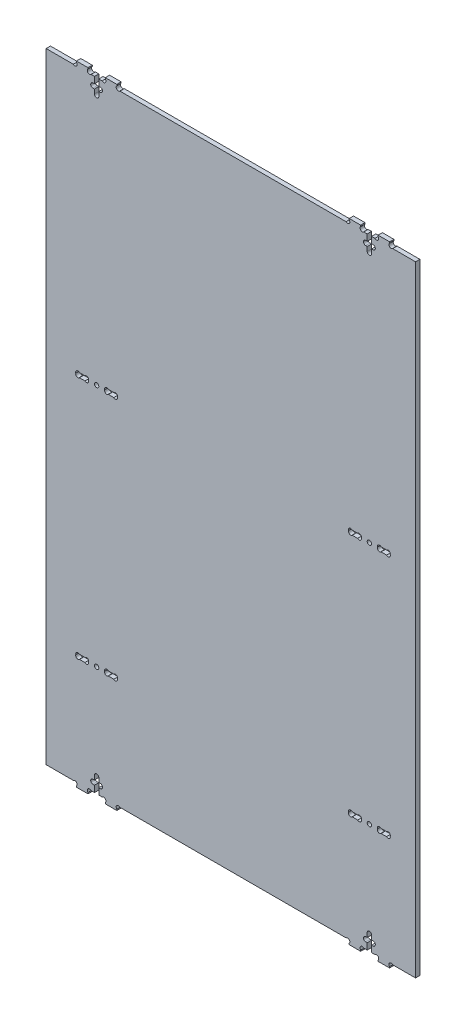
SolidWorks part; units mm, degrees
ref_plane "Спереди" through (0, 0, 0) normal (0, 0, 1) x (1, 0, 0)
ref_plane "Сверху" through (0, 0, 0) normal (0, 1, 0) x (1, 0, 0)
ref_plane "Справа" through (0, 0, 0) normal (1, 0, 0) x (0, 0, -1)
other "Configuration Table"
sketch "Эскиз1" plane through (0, 0, 0) normal (0, 0, 1) x (1, 0, 0)
  line L1 (0, -435.8) -> (-518, -435.8)
  line L2 (0, -435.8) -> (0, 435.8)
  line L3 (0, 435.8) -> (-518, 435.8)
  line L4 (-518, -435.8) -> (-518, 435.8)
  dimension "X001" = 518
  dimension "Y001" = 435.8
  dimension "Y002" = 435.8
extrude "Бобышка-Вытянуть1" add sketch "Эскиз1" against normal blind 6
sketch "Стыки_эскиз_пазов_и_стяжек_М5" plane through (0, 0, 0) normal (0, 0, 1) x (1, 0, 0)
  line L0 (-72.75, -415.65) -> (-74.15, -415.65)
  line L1 (-74.15, -415.65) -> (-74.15, -419.95)
  line L2 (-74.15, -419.95) -> (-72.75, -419.95)
  line L3 (-72.75, -419.95) -> (-72.75, -429.8)
  line L4 (-72.75, -429.8) -> (-82, -429.8)
  line L5 (-82, -429.8) -> (-82, -435.8)
  line L6 (-82, -435.8) -> (-72.75, -435.8)
  line L7 (-72.75, -435.8) -> (-72.75, -435.9)
  line L8 (-72.75, -435.9) -> (-67.25, -435.9)
  line L9 (-67.25, -435.9) -> (-67.25, -435.8)
  line L10 (-67.25, -435.8) -> (-58, -435.8)
  line L11 (-58, -435.8) -> (-58, -429.8)
  line L12 (-58, -429.8) -> (-67.25, -429.8)
  line L13 (-67.25, -429.8) -> (-67.25, -419.95)
  line L14 (-67.25, -419.95) -> (-65.85, -419.95)
  line L15 (-65.85, -419.95) -> (-65.85, -415.65)
  line L16 (-65.85, -415.65) -> (-67.25, -415.65)
  line L17 (-67.25, -415.65) -> (-67.25, -408.8)
  line L18 (-67.25, -408.8) -> (-72.75, -408.8)
  line L19 (-72.75, -408.8) -> (-72.75, -415.65)
  line L20 (-445.25, 419.95) -> (-445.25, 429.8)
  line L21 (-445.25, 429.8) -> (-436, 429.8)
  line L22 (-436, 429.8) -> (-436, 435.8)
  line L23 (-436, 435.8) -> (-445.25, 435.8)
  line L24 (-445.25, 435.8) -> (-445.25, 435.9)
  line L25 (-445.25, 435.9) -> (-450.75, 435.9)
  line L26 (-450.75, 435.9) -> (-450.75, 435.8)
  line L27 (-450.75, 435.8) -> (-460, 435.8)
  line L28 (-460, 435.8) -> (-460, 429.8)
  line L29 (-460, 429.8) -> (-450.75, 429.8)
  line L30 (-450.75, 429.8) -> (-450.75, 419.95)
  line L31 (-450.75, 419.95) -> (-452.15, 419.95)
  line L32 (-452.15, 419.95) -> (-452.15, 415.65)
  line L33 (-452.15, 415.65) -> (-450.75, 415.65)
  line L34 (-450.75, 415.65) -> (-450.75, 408.8)
  line L35 (-450.75, 408.8) -> (-445.25, 408.8)
  line L36 (-445.25, 408.8) -> (-445.25, 415.65)
  line L37 (-445.25, 415.65) -> (-443.85, 415.65)
  line L38 (-443.85, 415.65) -> (-443.85, 419.95)
  line L39 (-443.85, 419.95) -> (-445.25, 419.95)
  line L40 (-6, -429.8) -> (-42, -429.8)
  line L41 (-42, -429.8) -> (-42, -435.8)
  line L42 (-42, -435.8) -> (0.1, -435.8)
  line L43 (0.1, -435.8) -> (0.1, -429.8)
  line L44 (0.1, -429.8) -> (0, -429.8)
  line L45 (0, -429.8) -> (0, 429.8)
  line L46 (0, 429.8) -> (0.1, 429.8)
  line L47 (0.1, 429.8) -> (0.1, 435.8)
  line L48 (0.1, 435.8) -> (-42, 435.8)
  line L49 (-42, 435.8) -> (-42, 429.8)
  line L50 (-42, 429.8) -> (-6, 429.8)
  line L51 (-6, 429.8) -> (-6, -429.8)
  line L52 (-67.25, 435.8) -> (-67.25, 435.9)
  line L53 (-67.25, 435.9) -> (-72.75, 435.9)
  line L54 (-72.75, 435.9) -> (-72.75, 435.8)
  line L55 (-72.75, 435.8) -> (-82, 435.8)
  line L56 (-82, 435.8) -> (-82, 429.8)
  line L57 (-82, 429.8) -> (-72.75, 429.8)
  line L58 (-72.75, 429.8) -> (-72.75, 419.95)
  line L59 (-72.75, 419.95) -> (-74.15, 419.95)
  line L60 (-74.15, 419.95) -> (-74.15, 415.65)
  line L61 (-74.15, 415.65) -> (-72.75, 415.65)
  line L62 (-72.75, 415.65) -> (-72.75, 408.8)
  line L63 (-72.75, 408.8) -> (-67.25, 408.8)
  line L64 (-67.25, 408.8) -> (-67.25, 415.65)
  line L65 (-67.25, 415.65) -> (-65.85, 415.65)
  line L66 (-65.85, 415.65) -> (-65.85, 419.95)
  line L67 (-65.85, 419.95) -> (-67.25, 419.95)
  line L68 (-67.25, 419.95) -> (-67.25, 429.8)
  line L69 (-67.25, 429.8) -> (-58, 429.8)
  line L70 (-58, 429.8) -> (-58, 435.8)
  line L71 (-58, 435.8) -> (-67.25, 435.8)
  line L72 (-476.075, 63.875) -> (-476.075, 57.725)
  line L73 (-476.075, 57.725) -> (-459.925, 57.725)
  line L74 (-459.925, 57.725) -> (-459.925, 63.875)
  line L75 (-459.925, 63.875) -> (-476.075, 63.875)
  line L76 (-98, -435.8) -> (-98, -429.8)
  line L77 (-98, -429.8) -> (-420, -429.8)
  line L78 (-420, -429.8) -> (-420, -435.8)
  line L79 (-420, -435.8) -> (-98, -435.8)
  line L80 (-81.925, -274.125) -> (-98.075, -274.125)
  line L81 (-98.075, -274.125) -> (-98.075, -280.275)
  line L82 (-98.075, -280.275) -> (-81.925, -280.275)
  line L83 (-81.925, -280.275) -> (-81.925, -274.125)
  line L84 (-518.1, 435.8) -> (-518.1, 429.8)
  line L85 (-518.1, 429.8) -> (-476, 429.8)
  line L86 (-476, 429.8) -> (-476, 435.8)
  line L87 (-476, 435.8) -> (-518.1, 435.8)
  line L88 (-98.075, 63.875) -> (-98.075, 57.725)
  line L89 (-98.075, 57.725) -> (-81.925, 57.725)
  line L90 (-81.925, 57.725) -> (-81.925, 63.875)
  line L91 (-81.925, 63.875) -> (-98.075, 63.875)
  line L92 (-41.925, 57.725) -> (-41.925, 63.875)
  line L93 (-41.925, 63.875) -> (-58.075, 63.875)
  line L94 (-58.075, 63.875) -> (-58.075, 57.725)
  line L95 (-58.075, 57.725) -> (-41.925, 57.725)
  line L96 (-443.85, -419.95) -> (-443.85, -415.65)
  line L97 (-443.85, -415.65) -> (-445.25, -415.65)
  line L98 (-445.25, -415.65) -> (-445.25, -408.8)
  line L99 (-445.25, -408.8) -> (-450.75, -408.8)
  line L100 (-450.75, -408.8) -> (-450.75, -415.65)
  line L101 (-450.75, -415.65) -> (-452.15, -415.65)
  line L102 (-452.15, -415.65) -> (-452.15, -419.95)
  line L103 (-452.15, -419.95) -> (-450.75, -419.95)
  line L104 (-450.75, -419.95) -> (-450.75, -429.8)
  line L105 (-450.75, -429.8) -> (-460, -429.8)
  line L106 (-460, -429.8) -> (-460, -435.8)
  line L107 (-460, -435.8) -> (-450.75, -435.8)
  line L108 (-450.75, -435.8) -> (-450.75, -435.9)
  line L109 (-450.75, -435.9) -> (-445.25, -435.9)
  line L110 (-445.25, -435.9) -> (-445.25, -435.8)
  line L111 (-445.25, -435.8) -> (-436, -435.8)
  line L112 (-436, -435.8) -> (-436, -429.8)
  line L113 (-436, -429.8) -> (-445.25, -429.8)
  line L114 (-445.25, -429.8) -> (-445.25, -419.95)
  line L115 (-445.25, -419.95) -> (-443.85, -419.95)
  line L116 (-459.925, -280.275) -> (-459.925, -274.125)
  line L117 (-459.925, -274.125) -> (-476.075, -274.125)
  line L118 (-476.075, -274.125) -> (-476.075, -280.275)
  line L119 (-476.075, -280.275) -> (-459.925, -280.275)
  line L120 (-41.925, -280.275) -> (-41.925, -274.125)
  line L121 (-41.925, -274.125) -> (-58.075, -274.125)
  line L122 (-58.075, -274.125) -> (-58.075, -280.275)
  line L123 (-58.075, -280.275) -> (-41.925, -280.275)
  line L124 (-436.075, -274.125) -> (-436.075, -280.275)
  line L125 (-436.075, -280.275) -> (-419.925, -280.275)
  line L126 (-419.925, -280.275) -> (-419.925, -274.125)
  line L127 (-419.925, -274.125) -> (-436.075, -274.125)
  line L128 (-436.075, 63.875) -> (-436.075, 57.725)
  line L129 (-436.075, 57.725) -> (-419.925, 57.725)
  line L130 (-419.925, 57.725) -> (-419.925, 63.875)
  line L131 (-419.925, 63.875) -> (-436.075, 63.875)
  line L132 (-476, -429.8) -> (-518.1, -429.8)
  line L133 (-518.1, -429.8) -> (-518.1, -435.8)
  line L134 (-518.1, -435.8) -> (-476, -435.8)
  line L135 (-476, -435.8) -> (-476, -429.8)
  line L136 (-98, 429.8) -> (-98, 435.8)
  line L137 (-98, 435.8) -> (-420, 435.8)
  line L138 (-420, 435.8) -> (-420, 429.8)
  line L139 (-420, 429.8) -> (-98, 429.8)
  circle A0 centre (-448, -277.2) radius 2.75
  circle A1 centre (-448, 60.8) radius 2.75
  circle A2 centre (-70, -277.2) radius 2.75
  circle A3 centre (-70, 60.8) radius 2.75
  dimension "Диаметр001" = 5.5
  dimension "Диаметр002" = 5.5
  dimension "Диаметр003" = 5.5
  dimension "Диаметр004" = 5.5
  dimension "X001" = 518.1
  dimension "X002" = 476.075
  dimension "X003" = 476
  dimension "X004" = 460
  dimension "X005" = 459.925
  dimension "X006" = 452.15
  dimension "X007" = 450.75
  dimension "X008" = 448
  dimension "X009" = 445.25
  dimension "X010" = 443.85
  dimension "X011" = 436.075
  dimension "X012" = 436
  dimension "X013" = 420
  dimension "X014" = 419.925
  dimension "X015" = 98.075
  dimension "X016" = 98
  dimension "X017" = 82
  dimension "X018" = 81.925
  dimension "X019" = 74.15
  dimension "X020" = 72.75
  dimension "X021" = 70
  dimension "X022" = 67.25
  dimension "X023" = 65.85
  dimension "X024" = 58.075
  dimension "X025" = 58
  dimension "X026" = 42
  dimension "X027" = 41.925
  dimension "X028" = 6
  dimension "X029" = 0.1
  dimension "Y001" = 435.9
  dimension "Y002" = 435.8
  dimension "Y003" = 429.8
  dimension "Y004" = 419.95
  dimension "Y005" = 415.65
  dimension "Y006" = 408.8
  dimension "Y007" = 280.275
  dimension "Y008" = 277.2
  dimension "Y009" = 274.125
  dimension "Y010" = 57.725
  dimension "Y011" = 60.8
  dimension "Y012" = 63.875
  dimension "Y013" = 408.8
  dimension "Y014" = 415.65
  dimension "Y015" = 419.95
  dimension "Y016" = 429.8
  dimension "Y017" = 435.8
  dimension "Y018" = 435.9
extrude "Стыки_шип_паз_стяжки_М5" cut sketch "Стыки_эскиз_пазов_и_стяжек_М5" against normal through all and the other way through all
sketch "ЧПУ_М6_01_Центр" plane through (0, 0, 0) normal (0, 0, 1) x (1, 0, 0)
  line L0 (-74.15, -415.65) -> (-74.15, -419.95) construction
  line L1 (-74.15, -419.95) -> (-72.75, -419.95) construction
  point P0 (-70, -417.8)
  dimension "От_кромки_по_X" = 4.15
  dimension "От_кромки_по_Y" = 2.15
sketch "ЧПУ_М6_01_Канал_эскиз" plane through (0, 0, 0) normal (0, 0, 1) x (1, 0, 0)
  line L0 (-73, -429.9) -> (-67, -429.9)
  line L1 (-67, -429.9) -> (-67, -408.7)
  line L2 (-67, -408.7) -> (-73, -408.7)
  line L3 (-73, -408.7) -> (-73, -429.9)
  line L4 (-73, -429.9) -> (-67, -408.7) construction
  point P4 (-70, -419.3)
  dimension "Ширина" = 6
  dimension "Глубина" = 21.2
  dimension "Положение_ОтКромки" = 1.5
extrude "ЧПУ_М6_01_Канал" cut sketch "ЧПУ_М6_01_Канал_эскиз" against normal through all and the other way through all
sketch "ЧПУ_М6_01_Гайка_эскиз" plane through (0, 0, 0) normal (0, 0, 1) x (1, 0, 0)
  line L0 (-75.15, -420.9) -> (-64.85, -420.9)
  line L1 (-64.85, -420.9) -> (-64.85, -414.7)
  line L2 (-64.85, -414.7) -> (-75.15, -414.7)
  line L3 (-75.15, -414.7) -> (-75.15, -420.9)
  line L4 (-75.15, -420.9) -> (-64.85, -414.7) construction
  point P4 (-70, -417.8)
  dimension "Ширина" = 10.3
  dimension "Глубина" = 6.2
extrude "ЧПУ_М6_01_Гайка" cut sketch "ЧПУ_М6_01_Гайка_эскиз" against normal through all and the other way through all
sketch "ЧПУ_М6_01_Т_эскиз_1" plane through (0, 0, 0) normal (0, 0, 1) x (1, 0, 0)
  circle A0 centre (-64.85, -417.75) radius 3.05
  circle A1 centre (-75.15, -417.75) radius 3.05
  dimension "Диаметр1" = 6.1
  dimension "Диаметр2" = 6.1
  dimension "Центр1_ПоОси" = 5.15
  dimension "Центр1_ОтКромки" = 0.05
  dimension "Центр2_ПоОси" = 5.15
  dimension "Центр2_ОтКромки" = 0.05
extrude "ЧПУ_М6_01_Т_разгрузка_1" cut sketch "ЧПУ_М6_01_Т_эскиз_1" against normal through all and the other way through all
sketch "ЧПУ_М6_01_Т_эскиз_-1" plane through (0, 0, 0) normal (0, 0, 1) x (1, 0, 0)
  circle A0 centre (-64.85, -417.85) radius 3.05
  circle A1 centre (-75.15, -417.85) radius 3.05
  dimension "Диаметр1" = 6.1
  dimension "Диаметр2" = 6.1
  dimension "Центр1_ПоОси" = 5.15
  dimension "Центр1_ОтКромки" = 0.05
  dimension "Центр2_ПоОси" = 5.15
  dimension "Центр2_ОтКромки" = 0.05
extrude "ЧПУ_М6_01_Т_разгрузка_-1" cut sketch "ЧПУ_М6_01_Т_эскиз_-1" against normal through all and the other way through all
sketch "ЧПУ_М6_01_Конец_эскиз" plane through (0, 0, 0) normal (0, 0, 1) x (1, 0, 0)
  circle A0 centre (-70, -408.7) radius 3
  dimension "Центр1_ОтКромки" = 9.1
extrude "ЧПУ_М6_01_Конец" cut sketch "ЧПУ_М6_01_Конец_эскиз" against normal through all and the other way through all
sketch "ЧПУ_М6_02_Центр" plane through (0, 0, 0) normal (0, 0, 1) x (1, 0, 0)
  line L0 (-74.15, 419.95) -> (-74.15, 415.65) construction
  line L1 (-74.15, 415.65) -> (-72.75, 415.65) construction
  point P0 (-70, 417.8)
  dimension "От_кромки_по_X" = 4.15
  dimension "От_кромки_по_Y" = 2.15
sketch "ЧПУ_М6_02_Канал_эскиз" plane through (0, 0, 0) normal (0, 0, 1) x (1, 0, 0)
  line L0 (-73, 408.7) -> (-67, 408.7)
  line L1 (-67, 408.7) -> (-67, 429.9)
  line L2 (-67, 429.9) -> (-73, 429.9)
  line L3 (-73, 429.9) -> (-73, 408.7)
  line L4 (-73, 408.7) -> (-67, 429.9) construction
  point P4 (-70, 419.3)
  dimension "Ширина" = 6
  dimension "Глубина" = 21.2
  dimension "Положение_ОтКромки" = 1.5
extrude "ЧПУ_М6_02_Канал" cut sketch "ЧПУ_М6_02_Канал_эскиз" against normal through all and the other way through all
sketch "ЧПУ_М6_02_Гайка_эскиз" plane through (0, 0, 0) normal (0, 0, 1) x (1, 0, 0)
  line L0 (-75.15, 414.7) -> (-64.85, 414.7)
  line L1 (-64.85, 414.7) -> (-64.85, 420.9)
  line L2 (-64.85, 420.9) -> (-75.15, 420.9)
  line L3 (-75.15, 420.9) -> (-75.15, 414.7)
  line L4 (-75.15, 414.7) -> (-64.85, 420.9) construction
  point P4 (-70, 417.8)
  dimension "Ширина" = 10.3
  dimension "Глубина" = 6.2
extrude "ЧПУ_М6_02_Гайка" cut sketch "ЧПУ_М6_02_Гайка_эскиз" against normal through all and the other way through all
sketch "ЧПУ_М6_02_Т_эскиз_1" plane through (0, 0, 0) normal (0, 0, 1) x (1, 0, 0)
  circle A0 centre (-64.85, 417.85) radius 3.05
  circle A1 centre (-75.15, 417.85) radius 3.05
  dimension "Диаметр1" = 6.1
  dimension "Диаметр2" = 6.1
  dimension "Центр1_ПоОси" = 5.15
  dimension "Центр1_ОтКромки" = 0.05
  dimension "Центр2_ПоОси" = 5.15
  dimension "Центр2_ОтКромки" = 0.05
extrude "ЧПУ_М6_02_Т_разгрузка_1" cut sketch "ЧПУ_М6_02_Т_эскиз_1" against normal through all and the other way through all
sketch "ЧПУ_М6_02_Т_эскиз_-1" plane through (0, 0, 0) normal (0, 0, 1) x (1, 0, 0)
  circle A0 centre (-64.85, 417.75) radius 3.05
  circle A1 centre (-75.15, 417.75) radius 3.05
  dimension "Диаметр1" = 6.1
  dimension "Диаметр2" = 6.1
  dimension "Центр1_ПоОси" = 5.15
  dimension "Центр1_ОтКромки" = 0.05
  dimension "Центр2_ПоОси" = 5.15
  dimension "Центр2_ОтКромки" = 0.05
extrude "ЧПУ_М6_02_Т_разгрузка_-1" cut sketch "ЧПУ_М6_02_Т_эскиз_-1" against normal through all and the other way through all
sketch "ЧПУ_М6_02_Конец_эскиз" plane through (0, 0, 0) normal (0, 0, 1) x (1, 0, 0)
  circle A0 centre (-70, 408.7) radius 3
  dimension "Центр1_ОтКромки" = 9.1
extrude "ЧПУ_М6_02_Конец" cut sketch "ЧПУ_М6_02_Конец_эскиз" against normal through all and the other way through all
sketch "ЧПУ_М6_03_Центр" plane through (0, 0, 0) normal (0, 0, 1) x (1, 0, 0)
  line L0 (-452.15, 419.95) -> (-452.15, 415.65) construction
  line L1 (-452.15, 415.65) -> (-450.75, 415.65) construction
  point P0 (-448, 417.8)
  dimension "От_кромки_по_X" = 4.15
  dimension "От_кромки_по_Y" = 2.15
sketch "ЧПУ_М6_03_Канал_эскиз" plane through (0, 0, 0) normal (0, 0, 1) x (1, 0, 0)
  line L0 (-451, 408.7) -> (-445, 408.7)
  line L1 (-445, 408.7) -> (-445, 429.9)
  line L2 (-445, 429.9) -> (-451, 429.9)
  line L3 (-451, 429.9) -> (-451, 408.7)
  line L4 (-451, 408.7) -> (-445, 429.9) construction
  point P4 (-448, 419.3)
  dimension "Ширина" = 6
  dimension "Глубина" = 21.2
  dimension "Положение_ОтКромки" = 1.5
extrude "ЧПУ_М6_03_Канал" cut sketch "ЧПУ_М6_03_Канал_эскиз" against normal through all and the other way through all
sketch "ЧПУ_М6_03_Гайка_эскиз" plane through (0, 0, 0) normal (0, 0, 1) x (1, 0, 0)
  line L0 (-453.15, 414.7) -> (-442.85, 414.7)
  line L1 (-442.85, 414.7) -> (-442.85, 420.9)
  line L2 (-442.85, 420.9) -> (-453.15, 420.9)
  line L3 (-453.15, 420.9) -> (-453.15, 414.7)
  line L4 (-453.15, 414.7) -> (-442.85, 420.9) construction
  point P4 (-448, 417.8)
  dimension "Ширина" = 10.3
  dimension "Глубина" = 6.2
extrude "ЧПУ_М6_03_Гайка" cut sketch "ЧПУ_М6_03_Гайка_эскиз" against normal through all and the other way through all
sketch "ЧПУ_М6_03_Т_эскиз_1" plane through (0, 0, 0) normal (0, 0, 1) x (1, 0, 0)
  circle A0 centre (-442.85, 417.85) radius 3.05
  circle A1 centre (-453.15, 417.85) radius 3.05
  dimension "Диаметр1" = 6.1
  dimension "Диаметр2" = 6.1
  dimension "Центр1_ПоОси" = 5.15
  dimension "Центр1_ОтКромки" = 0.05
  dimension "Центр2_ПоОси" = 5.15
  dimension "Центр2_ОтКромки" = 0.05
extrude "ЧПУ_М6_03_Т_разгрузка_1" cut sketch "ЧПУ_М6_03_Т_эскиз_1" against normal through all and the other way through all
sketch "ЧПУ_М6_03_Т_эскиз_-1" plane through (0, 0, 0) normal (0, 0, 1) x (1, 0, 0)
  circle A0 centre (-442.85, 417.75) radius 3.05
  circle A1 centre (-453.15, 417.75) radius 3.05
  dimension "Диаметр1" = 6.1
  dimension "Диаметр2" = 6.1
  dimension "Центр1_ПоОси" = 5.15
  dimension "Центр1_ОтКромки" = 0.05
  dimension "Центр2_ПоОси" = 5.15
  dimension "Центр2_ОтКромки" = 0.05
extrude "ЧПУ_М6_03_Т_разгрузка_-1" cut sketch "ЧПУ_М6_03_Т_эскиз_-1" against normal through all and the other way through all
sketch "ЧПУ_М6_03_Конец_эскиз" plane through (0, 0, 0) normal (0, 0, 1) x (1, 0, 0)
  circle A0 centre (-448, 408.7) radius 3
  dimension "Центр1_ОтКромки" = 9.1
extrude "ЧПУ_М6_03_Конец" cut sketch "ЧПУ_М6_03_Конец_эскиз" against normal through all and the other way through all
sketch "ЧПУ_М6_04_Центр" plane through (0, 0, 0) normal (0, 0, 1) x (1, 0, 0)
  line L0 (-452.15, -415.65) -> (-452.15, -419.95) construction
  line L1 (-452.15, -419.95) -> (-450.75, -419.95) construction
  point P0 (-448, -417.8)
  dimension "От_кромки_по_X" = 4.15
  dimension "От_кромки_по_Y" = 2.15
sketch "ЧПУ_М6_04_Канал_эскиз" plane through (0, 0, 0) normal (0, 0, 1) x (1, 0, 0)
  line L0 (-451, -429.9) -> (-445, -429.9)
  line L1 (-445, -429.9) -> (-445, -408.7)
  line L2 (-445, -408.7) -> (-451, -408.7)
  line L3 (-451, -408.7) -> (-451, -429.9)
  line L4 (-451, -429.9) -> (-445, -408.7) construction
  point P4 (-448, -419.3)
  dimension "Ширина" = 6
  dimension "Глубина" = 21.2
  dimension "Положение_ОтКромки" = 1.5
extrude "ЧПУ_М6_04_Канал" cut sketch "ЧПУ_М6_04_Канал_эскиз" against normal through all and the other way through all
sketch "ЧПУ_М6_04_Гайка_эскиз" plane through (0, 0, 0) normal (0, 0, 1) x (1, 0, 0)
  line L0 (-453.15, -420.9) -> (-442.85, -420.9)
  line L1 (-442.85, -420.9) -> (-442.85, -414.7)
  line L2 (-442.85, -414.7) -> (-453.15, -414.7)
  line L3 (-453.15, -414.7) -> (-453.15, -420.9)
  line L4 (-453.15, -420.9) -> (-442.85, -414.7) construction
  point P4 (-448, -417.8)
  dimension "Ширина" = 10.3
  dimension "Глубина" = 6.2
extrude "ЧПУ_М6_04_Гайка" cut sketch "ЧПУ_М6_04_Гайка_эскиз" against normal through all and the other way through all
sketch "ЧПУ_М6_04_Т_эскиз_1" plane through (0, 0, 0) normal (0, 0, 1) x (1, 0, 0)
  circle A0 centre (-442.85, -417.75) radius 3.05
  circle A1 centre (-453.15, -417.75) radius 3.05
  dimension "Диаметр1" = 6.1
  dimension "Диаметр2" = 6.1
  dimension "Центр1_ПоОси" = 5.15
  dimension "Центр1_ОтКромки" = 0.05
  dimension "Центр2_ПоОси" = 5.15
  dimension "Центр2_ОтКромки" = 0.05
extrude "ЧПУ_М6_04_Т_разгрузка_1" cut sketch "ЧПУ_М6_04_Т_эскиз_1" against normal through all and the other way through all
sketch "ЧПУ_М6_04_Т_эскиз_-1" plane through (0, 0, 0) normal (0, 0, 1) x (1, 0, 0)
  circle A0 centre (-442.85, -417.85) radius 3.05
  circle A1 centre (-453.15, -417.85) radius 3.05
  dimension "Диаметр1" = 6.1
  dimension "Диаметр2" = 6.1
  dimension "Центр1_ПоОси" = 5.15
  dimension "Центр1_ОтКромки" = 0.05
  dimension "Центр2_ПоОси" = 5.15
  dimension "Центр2_ОтКромки" = 0.05
extrude "ЧПУ_М6_04_Т_разгрузка_-1" cut sketch "ЧПУ_М6_04_Т_эскиз_-1" against normal through all and the other way through all
sketch "ЧПУ_М6_04_Конец_эскиз" plane through (0, 0, 0) normal (0, 0, 1) x (1, 0, 0)
  circle A0 centre (-448, -408.7) radius 3
  dimension "Центр1_ОтКромки" = 9.1
extrude "ЧПУ_М6_04_Конец" cut sketch "ЧПУ_М6_04_Конец_эскиз" against normal through all and the other way through all
sketch "ЧПУ_Шаблон_углов_01" plane through (0, 0, 0) normal (0, 0, 1) x (1, 0, 0)
  line L0 (-58.075, -274.125) -> (-58.075, -280.275) construction
  line L1 (-58.075, -280.275) -> (-41.925, -280.275) construction
  line L2 (-476.075, -274.125) -> (-476.075, -280.275) construction
  line L3 (-476.075, -280.275) -> (-459.925, -280.275) construction
  line L4 (-42, 435.8) -> (-42, 429.8) construction
  line L5 (-42, 429.8) -> (-6, 429.8) construction
  line L6 (-82, 435.8) -> (-82, 429.8) construction
  line L7 (-82, 429.8) -> (-73, 429.8) construction
  line L8 (-420, 435.8) -> (-420, 429.8) construction
  line L9 (-420, 429.8) -> (-98, 429.8) construction
  line L10 (-460, 435.8) -> (-460, 429.8) construction
  line L11 (-460, 429.8) -> (-451, 429.8) construction
  line L12 (-58.075, 63.875) -> (-58.075, 57.725) construction
  line L13 (-58.075, 57.725) -> (-41.925, 57.725) construction
  line L14 (-436.075, 63.875) -> (-436.075, 57.725) construction
  line L15 (-436.075, 57.725) -> (-419.925, 57.725) construction
  line L16 (-436.075, -274.125) -> (-436.075, -280.275) construction
  line L17 (-436.075, -280.275) -> (-419.925, -280.275) construction
  line L18 (-476.075, 63.875) -> (-476.075, 57.725) construction
  line L19 (-476.075, 57.725) -> (-459.925, 57.725) construction
  line L20 (-98.075, -274.125) -> (-98.075, -280.275) construction
  line L21 (-98.075, -280.275) -> (-81.925, -280.275) construction
  line L22 (-98.075, 63.875) -> (-98.075, 57.725) construction
  line L23 (-98.075, 57.725) -> (-81.925, 57.725) construction
  circle A0 centre (-55.9537, -278.1537) radius 3.05
  circle A1 centre (-473.9537, -278.1537) radius 3.05
  circle A2 centre (-39.8787, 431.9213) radius 3.05
  circle A3 centre (-79.8787, 431.9213) radius 3.05
  circle A4 centre (-417.8787, 431.9213) radius 3.05
  circle A5 centre (-457.8787, 431.9213) radius 3.05
  circle A6 centre (-55.9537, 59.8463) radius 3.05
  circle A7 centre (-433.9537, 59.8463) radius 3.05
  circle A8 centre (-433.9537, -278.1537) radius 3.05
  circle A9 centre (-473.9537, 59.8463) radius 3.05
  circle A10 centre (-95.9537, -278.1537) radius 3.05
  circle A11 centre (-95.9537, 59.8463) radius 3.05
  dimension "D3" = 6.1
  dimension "D6" = 6.1
  dimension "D9" = 6.1
  dimension "D12" = 6.1
  dimension "D15" = 6.1
  dimension "D18" = 6.1
  dimension "D21" = 6.1
  dimension "D24" = 6.1
  dimension "D27" = 6.1
  dimension "D30" = 6.1
  dimension "D33" = 6.1
  dimension "D36" = 6.1
  dimension "D1" = 2.1213
  dimension "D2" = 2.1213
  dimension "D4" = 2.1213
  dimension "D5" = 2.1213
  dimension "D7" = 2.1213
  dimension "D8" = 2.1213
  dimension "D10" = 2.1213
  dimension "D11" = 2.1213
  dimension "D13" = 2.1213
  dimension "D14" = 2.1213
  dimension "D16" = 2.1213
  dimension "D17" = 2.1213
  dimension "D19" = 2.1213
  dimension "D20" = 2.1213
  dimension "D22" = 2.1213
  dimension "D23" = 2.1213
  dimension "D25" = 2.1213
  dimension "D26" = 2.1213
  dimension "D28" = 2.1213
  dimension "D29" = 2.1213
  dimension "D31" = 2.1213
  dimension "D32" = 2.1213
  dimension "D34" = 2.1213
  dimension "D35" = 2.1213
sketch "ЧПУ_Шаблон_углов_02" plane through (0, 0, 0) normal (0, 0, 1) x (1, 0, 0)
  line L0 (-58.075, -274.125) -> (-58.075, -280.275) construction
  line L1 (-41.925, -274.125) -> (-58.075, -274.125) construction
  line L2 (-476.075, -274.125) -> (-476.075, -280.275) construction
  line L3 (-459.925, -274.125) -> (-476.075, -274.125) construction
  line L4 (-420, -429.8) -> (-420, -435.8) construction
  line L5 (-98, -429.8) -> (-420, -429.8) construction
  line L6 (-82, -429.8) -> (-82, -435.8) construction
  line L7 (-73, -429.8) -> (-82, -429.8) construction
  line L8 (-42, -429.8) -> (-42, -435.8) construction
  line L9 (-6, -429.8) -> (-42, -429.8) construction
  line L10 (-460, -429.8) -> (-460, -435.8) construction
  line L11 (-451, -429.8) -> (-460, -429.8) construction
  line L12 (-58.075, 63.875) -> (-58.075, 57.725) construction
  line L13 (-41.925, 63.875) -> (-58.075, 63.875) construction
  line L14 (-436.075, 63.875) -> (-436.075, 57.725) construction
  line L15 (-419.925, 63.875) -> (-436.075, 63.875) construction
  line L16 (-436.075, -274.125) -> (-436.075, -280.275) construction
  line L17 (-419.925, -274.125) -> (-436.075, -274.125) construction
  line L18 (-476.075, 63.875) -> (-476.075, 57.725) construction
  line L19 (-459.925, 63.875) -> (-476.075, 63.875) construction
  line L20 (-98.075, -274.125) -> (-98.075, -280.275) construction
  line L21 (-81.925, -274.125) -> (-98.075, -274.125) construction
  line L22 (-98.075, 63.875) -> (-98.075, 57.725) construction
  line L23 (-81.925, 63.875) -> (-98.075, 63.875) construction
  circle A0 centre (-55.9537, -276.2463) radius 3.05
  circle A1 centre (-473.9537, -276.2463) radius 3.05
  circle A2 centre (-417.8787, -431.9213) radius 3.05
  circle A3 centre (-79.8787, -431.9213) radius 3.05
  circle A4 centre (-39.8787, -431.9213) radius 3.05
  circle A5 centre (-457.8787, -431.9213) radius 3.05
  circle A6 centre (-55.9537, 61.7537) radius 3.05
  circle A7 centre (-433.9537, 61.7537) radius 3.05
  circle A8 centre (-433.9537, -276.2463) radius 3.05
  circle A9 centre (-473.9537, 61.7537) radius 3.05
  circle A10 centre (-95.9537, -276.2463) radius 3.05
  circle A11 centre (-95.9537, 61.7537) radius 3.05
  dimension "D3" = 6.1
  dimension "D6" = 6.1
  dimension "D9" = 6.1
  dimension "D12" = 6.1
  dimension "D15" = 6.1
  dimension "D18" = 6.1
  dimension "D21" = 6.1
  dimension "D24" = 6.1
  dimension "D27" = 6.1
  dimension "D30" = 6.1
  dimension "D33" = 6.1
  dimension "D36" = 6.1
  dimension "D1" = 2.1213
  dimension "D2" = 2.1213
  dimension "D4" = 2.1213
  dimension "D5" = 2.1213
  dimension "D7" = 2.1213
  dimension "D8" = 2.1213
  dimension "D10" = 2.1213
  dimension "D11" = 2.1213
  dimension "D13" = 2.1213
  dimension "D14" = 2.1213
  dimension "D16" = 2.1213
  dimension "D17" = 2.1213
  dimension "D19" = 2.1213
  dimension "D20" = 2.1213
  dimension "D22" = 2.1213
  dimension "D23" = 2.1213
  dimension "D25" = 2.1213
  dimension "D26" = 2.1213
  dimension "D28" = 2.1213
  dimension "D29" = 2.1213
  dimension "D31" = 2.1213
  dimension "D32" = 2.1213
  dimension "D34" = 2.1213
  dimension "D35" = 2.1213
sketch "ЧПУ_Шаблон_углов_03" plane through (0, 0, 0) normal (0, 0, 1) x (1, 0, 0)
  line L0 (-41.925, -280.275) -> (-41.925, -274.125) construction
  line L1 (-58.075, -280.275) -> (-41.925, -280.275) construction
  line L2 (-459.925, -280.275) -> (-459.925, -274.125) construction
  line L3 (-476.075, -280.275) -> (-459.925, -280.275) construction
  line L4 (-58, 429.8) -> (-58, 435.8) construction
  line L5 (-67, 429.8) -> (-58, 429.8) construction
  line L6 (-98, 429.8) -> (-98, 435.8) construction
  line L7 (-420, 429.8) -> (-98, 429.8) construction
  line L8 (-436, 429.8) -> (-436, 435.8) construction
  line L9 (-445, 429.8) -> (-436, 429.8) construction
  line L10 (-476, 429.8) -> (-476, 435.8) construction
  line L11 (-518, 429.8) -> (-476, 429.8) construction
  line L12 (-41.925, 57.725) -> (-41.925, 63.875) construction
  line L13 (-58.075, 57.725) -> (-41.925, 57.725) construction
  line L14 (-419.925, 57.725) -> (-419.925, 63.875) construction
  line L15 (-436.075, 57.725) -> (-419.925, 57.725) construction
  line L16 (-419.925, -280.275) -> (-419.925, -274.125) construction
  line L17 (-436.075, -280.275) -> (-419.925, -280.275) construction
  line L18 (-459.925, 57.725) -> (-459.925, 63.875) construction
  line L19 (-476.075, 57.725) -> (-459.925, 57.725) construction
  line L20 (-81.925, -280.275) -> (-81.925, -274.125) construction
  line L21 (-98.075, -280.275) -> (-81.925, -280.275) construction
  line L22 (-81.925, 57.725) -> (-81.925, 63.875) construction
  line L23 (-98.075, 57.725) -> (-81.925, 57.725) construction
  circle A0 centre (-44.0463, -278.1537) radius 3.05
  circle A1 centre (-462.0463, -278.1537) radius 3.05
  circle A2 centre (-60.1213, 431.9213) radius 3.05
  circle A3 centre (-100.1213, 431.9213) radius 3.05
  circle A4 centre (-438.1213, 431.9213) radius 3.05
  circle A5 centre (-478.1213, 431.9213) radius 3.05
  circle A6 centre (-44.0463, 59.8463) radius 3.05
  circle A7 centre (-422.0463, 59.8463) radius 3.05
  circle A8 centre (-422.0463, -278.1537) radius 3.05
  circle A9 centre (-462.0463, 59.8463) radius 3.05
  circle A10 centre (-84.0463, -278.1537) radius 3.05
  circle A11 centre (-84.0463, 59.8463) radius 3.05
  dimension "D3" = 6.1
  dimension "D6" = 6.1
  dimension "D9" = 6.1
  dimension "D12" = 6.1
  dimension "D15" = 6.1
  dimension "D18" = 6.1
  dimension "D21" = 6.1
  dimension "D24" = 6.1
  dimension "D27" = 6.1
  dimension "D30" = 6.1
  dimension "D33" = 6.1
  dimension "D36" = 6.1
  dimension "D1" = 2.1213
  dimension "D2" = 2.1213
  dimension "D4" = 2.1213
  dimension "D5" = 2.1213
  dimension "D7" = 2.1213
  dimension "D8" = 2.1213
  dimension "D10" = 2.1213
  dimension "D11" = 2.1213
  dimension "D13" = 2.1213
  dimension "D14" = 2.1213
  dimension "D16" = 2.1213
  dimension "D17" = 2.1213
  dimension "D19" = 2.1213
  dimension "D20" = 2.1213
  dimension "D22" = 2.1213
  dimension "D23" = 2.1213
  dimension "D25" = 2.1213
  dimension "D26" = 2.1213
  dimension "D28" = 2.1213
  dimension "D29" = 2.1213
  dimension "D31" = 2.1213
  dimension "D32" = 2.1213
  dimension "D34" = 2.1213
  dimension "D35" = 2.1213
sketch "ЧПУ_Шаблон_углов_04" plane through (0, 0, 0) normal (0, 0, 1) x (1, 0, 0)
  line L0 (-41.925, -280.275) -> (-41.925, -274.125) construction
  line L1 (-41.925, -274.125) -> (-58.075, -274.125) construction
  line L2 (-459.925, -280.275) -> (-459.925, -274.125) construction
  line L3 (-459.925, -274.125) -> (-476.075, -274.125) construction
  line L4 (-98, -435.8) -> (-98, -429.8) construction
  line L5 (-98, -429.8) -> (-420, -429.8) construction
  line L6 (-58, -435.8) -> (-58, -429.8) construction
  line L7 (-58, -429.8) -> (-67, -429.8) construction
  line L8 (-476, -435.8) -> (-476, -429.8) construction
  line L9 (-476, -429.8) -> (-518, -429.8) construction
  line L10 (-436, -435.8) -> (-436, -429.8) construction
  line L11 (-436, -429.8) -> (-445, -429.8) construction
  line L12 (-41.925, 57.725) -> (-41.925, 63.875) construction
  line L13 (-41.925, 63.875) -> (-58.075, 63.875) construction
  line L14 (-419.925, 57.725) -> (-419.925, 63.875) construction
  line L15 (-419.925, 63.875) -> (-436.075, 63.875) construction
  line L16 (-419.925, -280.275) -> (-419.925, -274.125) construction
  line L17 (-419.925, -274.125) -> (-436.075, -274.125) construction
  line L18 (-459.925, 57.725) -> (-459.925, 63.875) construction
  line L19 (-459.925, 63.875) -> (-476.075, 63.875) construction
  line L20 (-81.925, -280.275) -> (-81.925, -274.125) construction
  line L21 (-81.925, -274.125) -> (-98.075, -274.125) construction
  line L22 (-81.925, 57.725) -> (-81.925, 63.875) construction
  line L23 (-81.925, 63.875) -> (-98.075, 63.875) construction
  circle A0 centre (-44.0463, -276.2463) radius 3.05
  circle A1 centre (-462.0463, -276.2463) radius 3.05
  circle A2 centre (-100.1213, -431.9213) radius 3.05
  circle A3 centre (-60.1213, -431.9213) radius 3.05
  circle A4 centre (-478.1213, -431.9213) radius 3.05
  circle A5 centre (-438.1213, -431.9213) radius 3.05
  circle A6 centre (-44.0463, 61.7537) radius 3.05
  circle A7 centre (-422.0463, 61.7537) radius 3.05
  circle A8 centre (-422.0463, -276.2463) radius 3.05
  circle A9 centre (-462.0463, 61.7537) radius 3.05
  circle A10 centre (-84.0463, -276.2463) radius 3.05
  circle A11 centre (-84.0463, 61.7537) radius 3.05
  dimension "D3" = 6.1
  dimension "D6" = 6.1
  dimension "D9" = 6.1
  dimension "D12" = 6.1
  dimension "D15" = 6.1
  dimension "D18" = 6.1
  dimension "D21" = 6.1
  dimension "D24" = 6.1
  dimension "D27" = 6.1
  dimension "D30" = 6.1
  dimension "D33" = 6.1
  dimension "D36" = 6.1
  dimension "D1" = 2.1213
  dimension "D2" = 2.1213
  dimension "D4" = 2.1213
  dimension "D5" = 2.1213
  dimension "D7" = 2.1213
  dimension "D8" = 2.1213
  dimension "D10" = 2.1213
  dimension "D11" = 2.1213
  dimension "D13" = 2.1213
  dimension "D14" = 2.1213
  dimension "D16" = 2.1213
  dimension "D17" = 2.1213
  dimension "D19" = 2.1213
  dimension "D20" = 2.1213
  dimension "D22" = 2.1213
  dimension "D23" = 2.1213
  dimension "D25" = 2.1213
  dimension "D26" = 2.1213
  dimension "D28" = 2.1213
  dimension "D29" = 2.1213
  dimension "D31" = 2.1213
  dimension "D32" = 2.1213
  dimension "D34" = 2.1213
  dimension "D35" = 2.1213
extrude "ЧПУ_Разгрузки_01" cut sketch "ЧПУ_Шаблон_углов_01" against normal through all and the other way through all
extrude "ЧПУ_Разгрузки_02" cut sketch "ЧПУ_Шаблон_углов_02" against normal through all and the other way through all
extrude "ЧПУ_Разгрузки_03" cut sketch "ЧПУ_Шаблон_углов_03" against normal through all and the other way through all
extrude "ЧПУ_Разгрузки_04" cut sketch "ЧПУ_Шаблон_углов_04" against normal through all and the other way through all
sketch "ЧПУ_Проход_М6_01_Ушко_эскиз" plane through (0, 0, 0) normal (0, 0, 1) x (1, 0, 0)
  circle A0 centre (-448, -277.2) radius 10
  circle A1 centre (-448, -277.2) radius 2.75 construction
  dimension "D1" = 20
extrude "ЧПУ_Проход_М6_01_Ушко20" add sketch "ЧПУ_Проход_М6_01_Ушко_эскиз" against normal blind 6
sketch "ЧПУ_Проход_М6_01_Отверстие_эскиз" plane through (0, 0, 0) normal (0, 0, 1) x (1, 0, 0)
  circle A0 centre (-448, -277.2) radius 3
extrude "ЧПУ_Проход_М6_01" cut sketch "ЧПУ_Проход_М6_01_Отверстие_эскиз" against normal through all and the other way through all
sketch "ЧПУ_Проход_М6_02_Ушко_эскиз" plane through (0, 0, 0) normal (0, 0, 1) x (1, 0, 0)
  circle A0 centre (-448, 60.8) radius 10
  circle A1 centre (-448, 60.8) radius 2.75 construction
  dimension "D1" = 20
extrude "ЧПУ_Проход_М6_02_Ушко20" add sketch "ЧПУ_Проход_М6_02_Ушко_эскиз" against normal blind 6
sketch "ЧПУ_Проход_М6_02_Отверстие_эскиз" plane through (0, 0, 0) normal (0, 0, 1) x (1, 0, 0)
  circle A0 centre (-448, 60.8) radius 3
extrude "ЧПУ_Проход_М6_02" cut sketch "ЧПУ_Проход_М6_02_Отверстие_эскиз" against normal through all and the other way through all
sketch "ЧПУ_Проход_М6_03_Ушко_эскиз" plane through (0, 0, 0) normal (0, 0, 1) x (1, 0, 0)
  circle A0 centre (-70, -277.2) radius 10
  circle A1 centre (-70, -277.2) radius 2.75 construction
  dimension "D1" = 20
extrude "ЧПУ_Проход_М6_03_Ушко20" add sketch "ЧПУ_Проход_М6_03_Ушко_эскиз" against normal blind 6
sketch "ЧПУ_Проход_М6_03_Отверстие_эскиз" plane through (0, 0, 0) normal (0, 0, 1) x (1, 0, 0)
  circle A0 centre (-70, -277.2) radius 3
extrude "ЧПУ_Проход_М6_03" cut sketch "ЧПУ_Проход_М6_03_Отверстие_эскиз" against normal through all and the other way through all
sketch "ЧПУ_Проход_М6_04_Ушко_эскиз" plane through (0, 0, 0) normal (0, 0, 1) x (1, 0, 0)
  circle A0 centre (-70, 60.8) radius 10
  circle A1 centre (-70, 60.8) radius 2.75 construction
  dimension "D1" = 20
extrude "ЧПУ_Проход_М6_04_Ушко20" add sketch "ЧПУ_Проход_М6_04_Ушко_эскиз" against normal blind 6
sketch "ЧПУ_Проход_М6_04_Отверстие_эскиз" plane through (0, 0, 0) normal (0, 0, 1) x (1, 0, 0)
  circle A0 centre (-70, 60.8) radius 3
extrude "ЧПУ_Проход_М6_04" cut sketch "ЧПУ_Проход_М6_04_Отверстие_эскиз" against normal through all and the other way through all
equation "\"Ширина груза\"= 420"
equation "\"Глубина груза\"= 490"
equation "\"Высота груза\"= 297"
equation "\"Ширина ячейки\"= \"Ширина груза\" + 10"
equation "\"Глубина ячейки\"= \"Глубина груза\" + 10"
equation "\"Высота ячейки\"= \"Высота груза\" + 10 + 13"
equation "\"Колво ячеек ширина\"= 2"
equation "\"Колво ячеек высота\"= 2"
equation "\"Толщина стенки\" = 6"
equation "\"Крепление дверцы\"= 5 "
equation "\"Ширина рейки\"= \"Толщина шестерни\""
equation "\"Высота рейки\"= 20"
equation "\"Высота пола\"= \"Толщина стенки\" * 2"
equation "\"Колво полозьев\"= 5"
equation "\"Отступ рейки\"= 20"
equation "\"Глубина каретки\"= \"Глубина ячейки\" + 30 + \"Мотор Y высота корпуса\" + 20"
equation "\"Длинна рейки\" = (\"Ширина ячейки\" + \"Толщина стенки\" + \"Крепление дверцы\") * \"Колво ячеек ширина\" + \"Ширина ячейки выгрузки\" * \"Колво выгрузки\" + \"Толщина стенки\" + \"Отступ крепления мотора фиксации\" * 2 - \"Крепление дверцы\" * \"Колво ячеек ширина\""
equation "\"Отступ шпильки\"= 26"
equation "\"Диаметр шпильки\"= 5"
equation "\"Длинна шпильки\"= ( \"Высота ячейки\" + \"Толщина стенки\" + \"Высота пола\" ) * \"Колво ячеек высота\" + ( \"Толщина стенки\" + \"Отступ рейки\" ) * 2 "
equation "\"Ширина пластины\"= 50  "
equation "\"Высота зона выгрузки\"= \"Высота ячейки\" * 2 + \"Толщина стенки\" * 2"
equation "\"Колво выгрузки\"= 1"
equation "\"Ширина ячейки выгрузки\"= \"Ширина ячейки\" + \"Толщина стенки\" + \"Отступ крепления мотора фиксации\"*2"
equation "\"Отступ крепления мотора фиксации\" = (\"Ширина пластины\" + 20 - \"Толщина стенки\") / 2"
equation "\"Мотор X ширина корпуса\"= 42.3"
equation "\"Мотор X высота корпуса\"= 42.3"
equation "\"Мотор X длина корпуса\"= 40"
equation "\"Мотор X вылет вала\"= 19.8"
equation "\"Мотор Y ширина корпуса\"= 42.3"
equation "\"Мотор Y высота корпуса\"= 42.3"
equation "\"Мотор Y длина корпуса\"= 48"
equation "\"Мотор Y вылет вала\"= 30"
equation "\"Мотор Z ширина корпуса\"= 42"
equation "\"Мотор Z высота корпуса\"= 42"
equation "\"Мотор Z длина корпуса\"= 40"
equation "\"Мотор Z вылет вала\"= 23"
equation "\"Мотор диаметр вала ПРЕДВ\"= 5"
equation "\"Мотор шаг крепления ПРЕДВ\"= 31"
equation "\"Мотор диаметр отверстий ПРЕДВ\"= 3"
equation "\"Мотор глубина отверстий ПРЕДВ\"= 4.5"
equation "\"Мотор диаметр буртика ПРЕДВ\"= 22"
equation "\"Мотор высота буртика ПРЕДВ\"= 2"
equation "\"Мотор диаметр шкива ПРЕДВ\"= 16"
equation "\"Мотор длина шкива ПРЕДВ\"= 12"
equation "\"Мотор отступ шкива ПРЕДВ\"= 5"
equation "\"Мотор X шаг градусов\"= 1.8"
equation "\"Мотор Y шаг градусов\"= 1.8"
equation "\"Мотор Z шаг градусов\"= 1.8"
equation "\"Мотор Y диаметр ротора\"= 25.78"
equation "\"Толщина шестерни\"= 10"
equation "\"D1@Бобышка-Вытянуть1\"=\"Толщина стенки\""
equation "\"Канал М6\"=6"
equation "\"Гайка под ключ\"=10.3"
equation "\"Длина кармана гайки\"=6.2"
equation "\"Основная фреза\"=6"
equation "\"Запас разгрузки\"=0.05"
equation "\"Ширина@ЧПУ_М6_01_Канал_эскиз\" = \"Канал М6\""
equation "\"Глубина@ЧПУ_М6_01_Канал_эскиз\" = 21.2"
equation "\"Положение_ОтКромки@ЧПУ_М6_01_Канал_эскиз\" =  -  (  - 1.5 ) "
equation "\"Ширина@ЧПУ_М6_01_Гайка_эскиз\" = \"Гайка под ключ\""
equation "\"Глубина@ЧПУ_М6_01_Гайка_эскиз\" = \"Длина кармана гайки\""
equation "\"Центр1_ПоОси@ЧПУ_М6_01_Т_эскиз_1\" =  ( \"Гайка под ключ\" / 2 ) "
equation "\"Центр1_ОтКромки@ЧПУ_М6_01_Т_эскиз_1\" =  ( 0.05 ) "
equation "\"Диаметр1@ЧПУ_М6_01_Т_эскиз_1\" = \"Основная фреза\" + 2 * \"Запас разгрузки\""
equation "\"Центр2_ПоОси@ЧПУ_М6_01_Т_эскиз_1\" =  -  (  - \"Гайка под ключ\" / 2 ) "
equation "\"Центр2_ОтКромки@ЧПУ_М6_01_Т_эскиз_1\" =  ( 0.05 ) "
equation "\"Диаметр2@ЧПУ_М6_01_Т_эскиз_1\" = \"Основная фреза\" + 2 * \"Запас разгрузки\""
equation "\"Центр1_ПоОси@ЧПУ_М6_01_Т_эскиз_-1\" =  ( \"Гайка под ключ\" / 2 ) "
equation "\"Центр1_ОтКромки@ЧПУ_М6_01_Т_эскиз_-1\" =  -  (  - 0.05 ) "
equation "\"Диаметр1@ЧПУ_М6_01_Т_эскиз_-1\" = \"Основная фреза\" + 2 * \"Запас разгрузки\""
equation "\"Центр2_ПоОси@ЧПУ_М6_01_Т_эскиз_-1\" =  -  (  - \"Гайка под ключ\" / 2 ) "
equation "\"Центр2_ОтКромки@ЧПУ_М6_01_Т_эскиз_-1\" =  -  (  - 0.05 ) "
equation "\"Диаметр2@ЧПУ_М6_01_Т_эскиз_-1\" = \"Основная фреза\" + 2 * \"Запас разгрузки\""
equation "\"Центр1_ОтКромки@ЧПУ_М6_01_Конец_эскиз\" =  ( 9.1 ) "
equation "\"Диаметр1@ЧПУ_М6_01_Конец_эскиз\" = \"Канал М6\""
equation "\"Ширина@ЧПУ_М6_02_Канал_эскиз\" = \"Канал М6\""
equation "\"Глубина@ЧПУ_М6_02_Канал_эскиз\" = 21.2"
equation "\"Положение_ОтКромки@ЧПУ_М6_02_Канал_эскиз\" =  ( 1.5 ) "
equation "\"Ширина@ЧПУ_М6_02_Гайка_эскиз\" = \"Гайка под ключ\""
equation "\"Глубина@ЧПУ_М6_02_Гайка_эскиз\" = \"Длина кармана гайки\""
equation "\"Центр1_ПоОси@ЧПУ_М6_02_Т_эскиз_1\" =  ( \"Гайка под ключ\" / 2 ) "
equation "\"Центр1_ОтКромки@ЧПУ_М6_02_Т_эскиз_1\" =  ( 0.05 ) "
equation "\"Диаметр1@ЧПУ_М6_02_Т_эскиз_1\" = \"Основная фреза\" + 2 * \"Запас разгрузки\""
equation "\"Центр2_ПоОси@ЧПУ_М6_02_Т_эскиз_1\" =  -  (  - \"Гайка под ключ\" / 2 ) "
equation "\"Центр2_ОтКромки@ЧПУ_М6_02_Т_эскиз_1\" =  ( 0.05 ) "
equation "\"Диаметр2@ЧПУ_М6_02_Т_эскиз_1\" = \"Основная фреза\" + 2 * \"Запас разгрузки\""
equation "\"Центр1_ПоОси@ЧПУ_М6_02_Т_эскиз_-1\" =  ( \"Гайка под ключ\" / 2 ) "
equation "\"Центр1_ОтКромки@ЧПУ_М6_02_Т_эскиз_-1\" =  -  (  - 0.05 ) "
equation "\"Диаметр1@ЧПУ_М6_02_Т_эскиз_-1\" = \"Основная фреза\" + 2 * \"Запас разгрузки\""
equation "\"Центр2_ПоОси@ЧПУ_М6_02_Т_эскиз_-1\" =  -  (  - \"Гайка под ключ\" / 2 ) "
equation "\"Центр2_ОтКромки@ЧПУ_М6_02_Т_эскиз_-1\" =  -  (  - 0.05 ) "
equation "\"Диаметр2@ЧПУ_М6_02_Т_эскиз_-1\" = \"Основная фреза\" + 2 * \"Запас разгрузки\""
equation "\"Центр1_ОтКромки@ЧПУ_М6_02_Конец_эскиз\" =  -  (  - 9.1 ) "
equation "\"Диаметр1@ЧПУ_М6_02_Конец_эскиз\" = \"Канал М6\""
equation "\"Ширина@ЧПУ_М6_03_Канал_эскиз\" = \"Канал М6\""
equation "\"Глубина@ЧПУ_М6_03_Канал_эскиз\" = 21.2"
equation "\"Положение_ОтКромки@ЧПУ_М6_03_Канал_эскиз\" =  ( 1.5 ) "
equation "\"Ширина@ЧПУ_М6_03_Гайка_эскиз\" = \"Гайка под ключ\""
equation "\"Глубина@ЧПУ_М6_03_Гайка_эскиз\" = \"Длина кармана гайки\""
equation "\"Центр1_ПоОси@ЧПУ_М6_03_Т_эскиз_1\" =  ( \"Гайка под ключ\" / 2 ) "
equation "\"Центр1_ОтКромки@ЧПУ_М6_03_Т_эскиз_1\" =  ( 0.05 ) "
equation "\"Диаметр1@ЧПУ_М6_03_Т_эскиз_1\" = \"Основная фреза\" + 2 * \"Запас разгрузки\""
equation "\"Центр2_ПоОси@ЧПУ_М6_03_Т_эскиз_1\" =  -  (  - \"Гайка под ключ\" / 2 ) "
equation "\"Центр2_ОтКромки@ЧПУ_М6_03_Т_эскиз_1\" =  ( 0.05 ) "
equation "\"Диаметр2@ЧПУ_М6_03_Т_эскиз_1\" = \"Основная фреза\" + 2 * \"Запас разгрузки\""
equation "\"Центр1_ПоОси@ЧПУ_М6_03_Т_эскиз_-1\" =  ( \"Гайка под ключ\" / 2 ) "
equation "\"Центр1_ОтКромки@ЧПУ_М6_03_Т_эскиз_-1\" =  -  (  - 0.05 ) "
equation "\"Диаметр1@ЧПУ_М6_03_Т_эскиз_-1\" = \"Основная фреза\" + 2 * \"Запас разгрузки\""
equation "\"Центр2_ПоОси@ЧПУ_М6_03_Т_эскиз_-1\" =  -  (  - \"Гайка под ключ\" / 2 ) "
equation "\"Центр2_ОтКромки@ЧПУ_М6_03_Т_эскиз_-1\" =  -  (  - 0.05 ) "
equation "\"Диаметр2@ЧПУ_М6_03_Т_эскиз_-1\" = \"Основная фреза\" + 2 * \"Запас разгрузки\""
equation "\"Центр1_ОтКромки@ЧПУ_М6_03_Конец_эскиз\" =  -  (  - 9.1 ) "
equation "\"Диаметр1@ЧПУ_М6_03_Конец_эскиз\" = \"Канал М6\""
equation "\"Ширина@ЧПУ_М6_04_Канал_эскиз\" = \"Канал М6\""
equation "\"Глубина@ЧПУ_М6_04_Канал_эскиз\" = 21.2"
equation "\"Положение_ОтКромки@ЧПУ_М6_04_Канал_эскиз\" =  -  (  - 1.5 ) "
equation "\"Ширина@ЧПУ_М6_04_Гайка_эскиз\" = \"Гайка под ключ\""
equation "\"Глубина@ЧПУ_М6_04_Гайка_эскиз\" = \"Длина кармана гайки\""
equation "\"Центр1_ПоОси@ЧПУ_М6_04_Т_эскиз_1\" =  ( \"Гайка под ключ\" / 2 ) "
equation "\"Центр1_ОтКромки@ЧПУ_М6_04_Т_эскиз_1\" =  ( 0.05 ) "
equation "\"Диаметр1@ЧПУ_М6_04_Т_эскиз_1\" = \"Основная фреза\" + 2 * \"Запас разгрузки\""
equation "\"Центр2_ПоОси@ЧПУ_М6_04_Т_эскиз_1\" =  -  (  - \"Гайка под ключ\" / 2 ) "
equation "\"Центр2_ОтКромки@ЧПУ_М6_04_Т_эскиз_1\" =  ( 0.05 ) "
equation "\"Диаметр2@ЧПУ_М6_04_Т_эскиз_1\" = \"Основная фреза\" + 2 * \"Запас разгрузки\""
equation "\"Центр1_ПоОси@ЧПУ_М6_04_Т_эскиз_-1\" =  ( \"Гайка под ключ\" / 2 ) "
equation "\"Центр1_ОтКромки@ЧПУ_М6_04_Т_эскиз_-1\" =  -  (  - 0.05 ) "
equation "\"Диаметр1@ЧПУ_М6_04_Т_эскиз_-1\" = \"Основная фреза\" + 2 * \"Запас разгрузки\""
equation "\"Центр2_ПоОси@ЧПУ_М6_04_Т_эскиз_-1\" =  -  (  - \"Гайка под ключ\" / 2 ) "
equation "\"Центр2_ОтКромки@ЧПУ_М6_04_Т_эскиз_-1\" =  -  (  - 0.05 ) "
equation "\"Диаметр2@ЧПУ_М6_04_Т_эскиз_-1\" = \"Основная фреза\" + 2 * \"Запас разгрузки\""
equation "\"Центр1_ОтКромки@ЧПУ_М6_04_Конец_эскиз\" =  ( 9.1 ) "
equation "\"Диаметр1@ЧПУ_М6_04_Конец_эскиз\" = \"Канал М6\""
equation "\"Фреза стыка\"= 6"
equation "\"Перебег разгрузки\"= 0.05"
equation "\"D1@ЧПУ_Шаблон_углов_01\" = \"Фреза стыка\" /  ( 2 * sqr ( 2 )  ) "
equation "\"D2@ЧПУ_Шаблон_углов_01\" = \"Фреза стыка\" /  ( 2 * sqr ( 2 )  ) "
equation "\"D3@ЧПУ_Шаблон_углов_01\" = \"Фреза стыка\" + 2 * \"Перебег разгрузки\""
equation "\"D4@ЧПУ_Шаблон_углов_01\" = \"Фреза стыка\" /  ( 2 * sqr ( 2 )  ) "
equation "\"D5@ЧПУ_Шаблон_углов_01\" = \"Фреза стыка\" /  ( 2 * sqr ( 2 )  ) "
equation "\"D6@ЧПУ_Шаблон_углов_01\" = \"Фреза стыка\" + 2 * \"Перебег разгрузки\""
equation "\"D7@ЧПУ_Шаблон_углов_01\" = \"Фреза стыка\" /  ( 2 * sqr ( 2 )  ) "
equation "\"D8@ЧПУ_Шаблон_углов_01\" = \"Фреза стыка\" /  ( 2 * sqr ( 2 )  ) "
equation "\"D9@ЧПУ_Шаблон_углов_01\" = \"Фреза стыка\" + 2 * \"Перебег разгрузки\""
equation "\"D10@ЧПУ_Шаблон_углов_01\" = \"Фреза стыка\" /  ( 2 * sqr ( 2 )  ) "
equation "\"D11@ЧПУ_Шаблон_углов_01\" = \"Фреза стыка\" /  ( 2 * sqr ( 2 )  ) "
equation "\"D12@ЧПУ_Шаблон_углов_01\" = \"Фреза стыка\" + 2 * \"Перебег разгрузки\""
equation "\"D13@ЧПУ_Шаблон_углов_01\" = \"Фреза стыка\" /  ( 2 * sqr ( 2 )  ) "
equation "\"D14@ЧПУ_Шаблон_углов_01\" = \"Фреза стыка\" /  ( 2 * sqr ( 2 )  ) "
equation "\"D15@ЧПУ_Шаблон_углов_01\" = \"Фреза стыка\" + 2 * \"Перебег разгрузки\""
equation "\"D16@ЧПУ_Шаблон_углов_01\" = \"Фреза стыка\" /  ( 2 * sqr ( 2 )  ) "
equation "\"D17@ЧПУ_Шаблон_углов_01\" = \"Фреза стыка\" /  ( 2 * sqr ( 2 )  ) "
equation "\"D18@ЧПУ_Шаблон_углов_01\" = \"Фреза стыка\" + 2 * \"Перебег разгрузки\""
equation "\"D19@ЧПУ_Шаблон_углов_01\" = \"Фреза стыка\" /  ( 2 * sqr ( 2 )  ) "
equation "\"D20@ЧПУ_Шаблон_углов_01\" = \"Фреза стыка\" /  ( 2 * sqr ( 2 )  ) "
equation "\"D21@ЧПУ_Шаблон_углов_01\" = \"Фреза стыка\" + 2 * \"Перебег разгрузки\""
equation "\"D22@ЧПУ_Шаблон_углов_01\" = \"Фреза стыка\" /  ( 2 * sqr ( 2 )  ) "
equation "\"D23@ЧПУ_Шаблон_углов_01\" = \"Фреза стыка\" /  ( 2 * sqr ( 2 )  ) "
equation "\"D24@ЧПУ_Шаблон_углов_01\" = \"Фреза стыка\" + 2 * \"Перебег разгрузки\""
equation "\"D25@ЧПУ_Шаблон_углов_01\" = \"Фреза стыка\" /  ( 2 * sqr ( 2 )  ) "
equation "\"D26@ЧПУ_Шаблон_углов_01\" = \"Фреза стыка\" /  ( 2 * sqr ( 2 )  ) "
equation "\"D27@ЧПУ_Шаблон_углов_01\" = \"Фреза стыка\" + 2 * \"Перебег разгрузки\""
equation "\"D28@ЧПУ_Шаблон_углов_01\" = \"Фреза стыка\" /  ( 2 * sqr ( 2 )  ) "
equation "\"D29@ЧПУ_Шаблон_углов_01\" = \"Фреза стыка\" /  ( 2 * sqr ( 2 )  ) "
equation "\"D30@ЧПУ_Шаблон_углов_01\" = \"Фреза стыка\" + 2 * \"Перебег разгрузки\""
equation "\"D31@ЧПУ_Шаблон_углов_01\" = \"Фреза стыка\" /  ( 2 * sqr ( 2 )  ) "
equation "\"D32@ЧПУ_Шаблон_углов_01\" = \"Фреза стыка\" /  ( 2 * sqr ( 2 )  ) "
equation "\"D33@ЧПУ_Шаблон_углов_01\" = \"Фреза стыка\" + 2 * \"Перебег разгрузки\""
equation "\"D34@ЧПУ_Шаблон_углов_01\" = \"Фреза стыка\" /  ( 2 * sqr ( 2 )  ) "
equation "\"D35@ЧПУ_Шаблон_углов_01\" = \"Фреза стыка\" /  ( 2 * sqr ( 2 )  ) "
equation "\"D36@ЧПУ_Шаблон_углов_01\" = \"Фреза стыка\" + 2 * \"Перебег разгрузки\""
equation "\"D1@ЧПУ_Шаблон_углов_02\" = \"Фреза стыка\" /  ( 2 * sqr ( 2 )  ) "
equation "\"D2@ЧПУ_Шаблон_углов_02\" = \"Фреза стыка\" /  ( 2 * sqr ( 2 )  ) "
equation "\"D3@ЧПУ_Шаблон_углов_02\" = \"Фреза стыка\" + 2 * \"Перебег разгрузки\""
equation "\"D4@ЧПУ_Шаблон_углов_02\" = \"Фреза стыка\" /  ( 2 * sqr ( 2 )  ) "
equation "\"D5@ЧПУ_Шаблон_углов_02\" = \"Фреза стыка\" /  ( 2 * sqr ( 2 )  ) "
equation "\"D6@ЧПУ_Шаблон_углов_02\" = \"Фреза стыка\" + 2 * \"Перебег разгрузки\""
equation "\"D7@ЧПУ_Шаблон_углов_02\" = \"Фреза стыка\" /  ( 2 * sqr ( 2 )  ) "
equation "\"D8@ЧПУ_Шаблон_углов_02\" = \"Фреза стыка\" /  ( 2 * sqr ( 2 )  ) "
equation "\"D9@ЧПУ_Шаблон_углов_02\" = \"Фреза стыка\" + 2 * \"Перебег разгрузки\""
equation "\"D10@ЧПУ_Шаблон_углов_02\" = \"Фреза стыка\" /  ( 2 * sqr ( 2 )  ) "
equation "\"D11@ЧПУ_Шаблон_углов_02\" = \"Фреза стыка\" /  ( 2 * sqr ( 2 )  ) "
equation "\"D12@ЧПУ_Шаблон_углов_02\" = \"Фреза стыка\" + 2 * \"Перебег разгрузки\""
equation "\"D13@ЧПУ_Шаблон_углов_02\" = \"Фреза стыка\" /  ( 2 * sqr ( 2 )  ) "
equation "\"D14@ЧПУ_Шаблон_углов_02\" = \"Фреза стыка\" /  ( 2 * sqr ( 2 )  ) "
equation "\"D15@ЧПУ_Шаблон_углов_02\" = \"Фреза стыка\" + 2 * \"Перебег разгрузки\""
equation "\"D16@ЧПУ_Шаблон_углов_02\" = \"Фреза стыка\" /  ( 2 * sqr ( 2 )  ) "
equation "\"D17@ЧПУ_Шаблон_углов_02\" = \"Фреза стыка\" /  ( 2 * sqr ( 2 )  ) "
equation "\"D18@ЧПУ_Шаблон_углов_02\" = \"Фреза стыка\" + 2 * \"Перебег разгрузки\""
equation "\"D19@ЧПУ_Шаблон_углов_02\" = \"Фреза стыка\" /  ( 2 * sqr ( 2 )  ) "
equation "\"D20@ЧПУ_Шаблон_углов_02\" = \"Фреза стыка\" /  ( 2 * sqr ( 2 )  ) "
equation "\"D21@ЧПУ_Шаблон_углов_02\" = \"Фреза стыка\" + 2 * \"Перебег разгрузки\""
equation "\"D22@ЧПУ_Шаблон_углов_02\" = \"Фреза стыка\" /  ( 2 * sqr ( 2 )  ) "
equation "\"D23@ЧПУ_Шаблон_углов_02\" = \"Фреза стыка\" /  ( 2 * sqr ( 2 )  ) "
equation "\"D24@ЧПУ_Шаблон_углов_02\" = \"Фреза стыка\" + 2 * \"Перебег разгрузки\""
equation "\"D25@ЧПУ_Шаблон_углов_02\" = \"Фреза стыка\" /  ( 2 * sqr ( 2 )  ) "
equation "\"D26@ЧПУ_Шаблон_углов_02\" = \"Фреза стыка\" /  ( 2 * sqr ( 2 )  ) "
equation "\"D27@ЧПУ_Шаблон_углов_02\" = \"Фреза стыка\" + 2 * \"Перебег разгрузки\""
equation "\"D28@ЧПУ_Шаблон_углов_02\" = \"Фреза стыка\" /  ( 2 * sqr ( 2 )  ) "
equation "\"D29@ЧПУ_Шаблон_углов_02\" = \"Фреза стыка\" /  ( 2 * sqr ( 2 )  ) "
equation "\"D30@ЧПУ_Шаблон_углов_02\" = \"Фреза стыка\" + 2 * \"Перебег разгрузки\""
equation "\"D31@ЧПУ_Шаблон_углов_02\" = \"Фреза стыка\" /  ( 2 * sqr ( 2 )  ) "
equation "\"D32@ЧПУ_Шаблон_углов_02\" = \"Фреза стыка\" /  ( 2 * sqr ( 2 )  ) "
equation "\"D33@ЧПУ_Шаблон_углов_02\" = \"Фреза стыка\" + 2 * \"Перебег разгрузки\""
equation "\"D34@ЧПУ_Шаблон_углов_02\" = \"Фреза стыка\" /  ( 2 * sqr ( 2 )  ) "
equation "\"D35@ЧПУ_Шаблон_углов_02\" = \"Фреза стыка\" /  ( 2 * sqr ( 2 )  ) "
equation "\"D36@ЧПУ_Шаблон_углов_02\" = \"Фреза стыка\" + 2 * \"Перебег разгрузки\""
equation "\"D1@ЧПУ_Шаблон_углов_03\" = \"Фреза стыка\" /  ( 2 * sqr ( 2 )  ) "
equation "\"D2@ЧПУ_Шаблон_углов_03\" = \"Фреза стыка\" /  ( 2 * sqr ( 2 )  ) "
equation "\"D3@ЧПУ_Шаблон_углов_03\" = \"Фреза стыка\" + 2 * \"Перебег разгрузки\""
equation "\"D4@ЧПУ_Шаблон_углов_03\" = \"Фреза стыка\" /  ( 2 * sqr ( 2 )  ) "
equation "\"D5@ЧПУ_Шаблон_углов_03\" = \"Фреза стыка\" /  ( 2 * sqr ( 2 )  ) "
equation "\"D6@ЧПУ_Шаблон_углов_03\" = \"Фреза стыка\" + 2 * \"Перебег разгрузки\""
equation "\"D7@ЧПУ_Шаблон_углов_03\" = \"Фреза стыка\" /  ( 2 * sqr ( 2 )  ) "
equation "\"D8@ЧПУ_Шаблон_углов_03\" = \"Фреза стыка\" /  ( 2 * sqr ( 2 )  ) "
equation "\"D9@ЧПУ_Шаблон_углов_03\" = \"Фреза стыка\" + 2 * \"Перебег разгрузки\""
equation "\"D10@ЧПУ_Шаблон_углов_03\" = \"Фреза стыка\" /  ( 2 * sqr ( 2 )  ) "
equation "\"D11@ЧПУ_Шаблон_углов_03\" = \"Фреза стыка\" /  ( 2 * sqr ( 2 )  ) "
equation "\"D12@ЧПУ_Шаблон_углов_03\" = \"Фреза стыка\" + 2 * \"Перебег разгрузки\""
equation "\"D13@ЧПУ_Шаблон_углов_03\" = \"Фреза стыка\" /  ( 2 * sqr ( 2 )  ) "
equation "\"D14@ЧПУ_Шаблон_углов_03\" = \"Фреза стыка\" /  ( 2 * sqr ( 2 )  ) "
equation "\"D15@ЧПУ_Шаблон_углов_03\" = \"Фреза стыка\" + 2 * \"Перебег разгрузки\""
equation "\"D16@ЧПУ_Шаблон_углов_03\" = \"Фреза стыка\" /  ( 2 * sqr ( 2 )  ) "
equation "\"D17@ЧПУ_Шаблон_углов_03\" = \"Фреза стыка\" /  ( 2 * sqr ( 2 )  ) "
equation "\"D18@ЧПУ_Шаблон_углов_03\" = \"Фреза стыка\" + 2 * \"Перебег разгрузки\""
equation "\"D19@ЧПУ_Шаблон_углов_03\" = \"Фреза стыка\" /  ( 2 * sqr ( 2 )  ) "
equation "\"D20@ЧПУ_Шаблон_углов_03\" = \"Фреза стыка\" /  ( 2 * sqr ( 2 )  ) "
equation "\"D21@ЧПУ_Шаблон_углов_03\" = \"Фреза стыка\" + 2 * \"Перебег разгрузки\""
equation "\"D22@ЧПУ_Шаблон_углов_03\" = \"Фреза стыка\" /  ( 2 * sqr ( 2 )  ) "
equation "\"D23@ЧПУ_Шаблон_углов_03\" = \"Фреза стыка\" /  ( 2 * sqr ( 2 )  ) "
equation "\"D24@ЧПУ_Шаблон_углов_03\" = \"Фреза стыка\" + 2 * \"Перебег разгрузки\""
equation "\"D25@ЧПУ_Шаблон_углов_03\" = \"Фреза стыка\" /  ( 2 * sqr ( 2 )  ) "
equation "\"D26@ЧПУ_Шаблон_углов_03\" = \"Фреза стыка\" /  ( 2 * sqr ( 2 )  ) "
equation "\"D27@ЧПУ_Шаблон_углов_03\" = \"Фреза стыка\" + 2 * \"Перебег разгрузки\""
equation "\"D28@ЧПУ_Шаблон_углов_03\" = \"Фреза стыка\" /  ( 2 * sqr ( 2 )  ) "
equation "\"D29@ЧПУ_Шаблон_углов_03\" = \"Фреза стыка\" /  ( 2 * sqr ( 2 )  ) "
equation "\"D30@ЧПУ_Шаблон_углов_03\" = \"Фреза стыка\" + 2 * \"Перебег разгрузки\""
equation "\"D31@ЧПУ_Шаблон_углов_03\" = \"Фреза стыка\" /  ( 2 * sqr ( 2 )  ) "
equation "\"D32@ЧПУ_Шаблон_углов_03\" = \"Фреза стыка\" /  ( 2 * sqr ( 2 )  ) "
equation "\"D33@ЧПУ_Шаблон_углов_03\" = \"Фреза стыка\" + 2 * \"Перебег разгрузки\""
equation "\"D34@ЧПУ_Шаблон_углов_03\" = \"Фреза стыка\" /  ( 2 * sqr ( 2 )  ) "
equation "\"D35@ЧПУ_Шаблон_углов_03\" = \"Фреза стыка\" /  ( 2 * sqr ( 2 )  ) "
equation "\"D36@ЧПУ_Шаблон_углов_03\" = \"Фреза стыка\" + 2 * \"Перебег разгрузки\""
equation "\"D1@ЧПУ_Шаблон_углов_04\" = \"Фреза стыка\" /  ( 2 * sqr ( 2 )  ) "
equation "\"D2@ЧПУ_Шаблон_углов_04\" = \"Фреза стыка\" /  ( 2 * sqr ( 2 )  ) "
equation "\"D3@ЧПУ_Шаблон_углов_04\" = \"Фреза стыка\" + 2 * \"Перебег разгрузки\""
equation "\"D4@ЧПУ_Шаблон_углов_04\" = \"Фреза стыка\" /  ( 2 * sqr ( 2 )  ) "
equation "\"D5@ЧПУ_Шаблон_углов_04\" = \"Фреза стыка\" /  ( 2 * sqr ( 2 )  ) "
equation "\"D6@ЧПУ_Шаблон_углов_04\" = \"Фреза стыка\" + 2 * \"Перебег разгрузки\""
equation "\"D7@ЧПУ_Шаблон_углов_04\" = \"Фреза стыка\" /  ( 2 * sqr ( 2 )  ) "
equation "\"D8@ЧПУ_Шаблон_углов_04\" = \"Фреза стыка\" /  ( 2 * sqr ( 2 )  ) "
equation "\"D9@ЧПУ_Шаблон_углов_04\" = \"Фреза стыка\" + 2 * \"Перебег разгрузки\""
equation "\"D10@ЧПУ_Шаблон_углов_04\" = \"Фреза стыка\" /  ( 2 * sqr ( 2 )  ) "
equation "\"D11@ЧПУ_Шаблон_углов_04\" = \"Фреза стыка\" /  ( 2 * sqr ( 2 )  ) "
equation "\"D12@ЧПУ_Шаблон_углов_04\" = \"Фреза стыка\" + 2 * \"Перебег разгрузки\""
equation "\"D13@ЧПУ_Шаблон_углов_04\" = \"Фреза стыка\" /  ( 2 * sqr ( 2 )  ) "
equation "\"D14@ЧПУ_Шаблон_углов_04\" = \"Фреза стыка\" /  ( 2 * sqr ( 2 )  ) "
equation "\"D15@ЧПУ_Шаблон_углов_04\" = \"Фреза стыка\" + 2 * \"Перебег разгрузки\""
equation "\"D16@ЧПУ_Шаблон_углов_04\" = \"Фреза стыка\" /  ( 2 * sqr ( 2 )  ) "
equation "\"D17@ЧПУ_Шаблон_углов_04\" = \"Фреза стыка\" /  ( 2 * sqr ( 2 )  ) "
equation "\"D18@ЧПУ_Шаблон_углов_04\" = \"Фреза стыка\" + 2 * \"Перебег разгрузки\""
equation "\"D19@ЧПУ_Шаблон_углов_04\" = \"Фреза стыка\" /  ( 2 * sqr ( 2 )  ) "
equation "\"D20@ЧПУ_Шаблон_углов_04\" = \"Фреза стыка\" /  ( 2 * sqr ( 2 )  ) "
equation "\"D21@ЧПУ_Шаблон_углов_04\" = \"Фреза стыка\" + 2 * \"Перебег разгрузки\""
equation "\"D22@ЧПУ_Шаблон_углов_04\" = \"Фреза стыка\" /  ( 2 * sqr ( 2 )  ) "
equation "\"D23@ЧПУ_Шаблон_углов_04\" = \"Фреза стыка\" /  ( 2 * sqr ( 2 )  ) "
equation "\"D24@ЧПУ_Шаблон_углов_04\" = \"Фреза стыка\" + 2 * \"Перебег разгрузки\""
equation "\"D25@ЧПУ_Шаблон_углов_04\" = \"Фреза стыка\" /  ( 2 * sqr ( 2 )  ) "
equation "\"D26@ЧПУ_Шаблон_углов_04\" = \"Фреза стыка\" /  ( 2 * sqr ( 2 )  ) "
equation "\"D27@ЧПУ_Шаблон_углов_04\" = \"Фреза стыка\" + 2 * \"Перебег разгрузки\""
equation "\"D28@ЧПУ_Шаблон_углов_04\" = \"Фреза стыка\" /  ( 2 * sqr ( 2 )  ) "
equation "\"D29@ЧПУ_Шаблон_углов_04\" = \"Фреза стыка\" /  ( 2 * sqr ( 2 )  ) "
equation "\"D30@ЧПУ_Шаблон_углов_04\" = \"Фреза стыка\" + 2 * \"Перебег разгрузки\""
equation "\"D31@ЧПУ_Шаблон_углов_04\" = \"Фреза стыка\" /  ( 2 * sqr ( 2 )  ) "
equation "\"D32@ЧПУ_Шаблон_углов_04\" = \"Фреза стыка\" /  ( 2 * sqr ( 2 )  ) "
equation "\"D33@ЧПУ_Шаблон_углов_04\" = \"Фреза стыка\" + 2 * \"Перебег разгрузки\""
equation "\"D34@ЧПУ_Шаблон_углов_04\" = \"Фреза стыка\" /  ( 2 * sqr ( 2 )  ) "
equation "\"D35@ЧПУ_Шаблон_углов_04\" = \"Фреза стыка\" /  ( 2 * sqr ( 2 )  ) "
equation "\"D36@ЧПУ_Шаблон_углов_04\" = \"Фреза стыка\" + 2 * \"Перебег разгрузки\""
equation "\"Диаметр1@ЧПУ_Проход_М6_01_Отверстие_эскиз\" = \"Канал М6\""
equation "\"Диаметр1@ЧПУ_Проход_М6_02_Отверстие_эскиз\" = \"Канал М6\""
equation "\"Диаметр1@ЧПУ_Проход_М6_03_Отверстие_эскиз\" = \"Канал М6\""
equation "\"Диаметр1@ЧПУ_Проход_М6_04_Отверстие_эскиз\" = \"Канал М6\""
